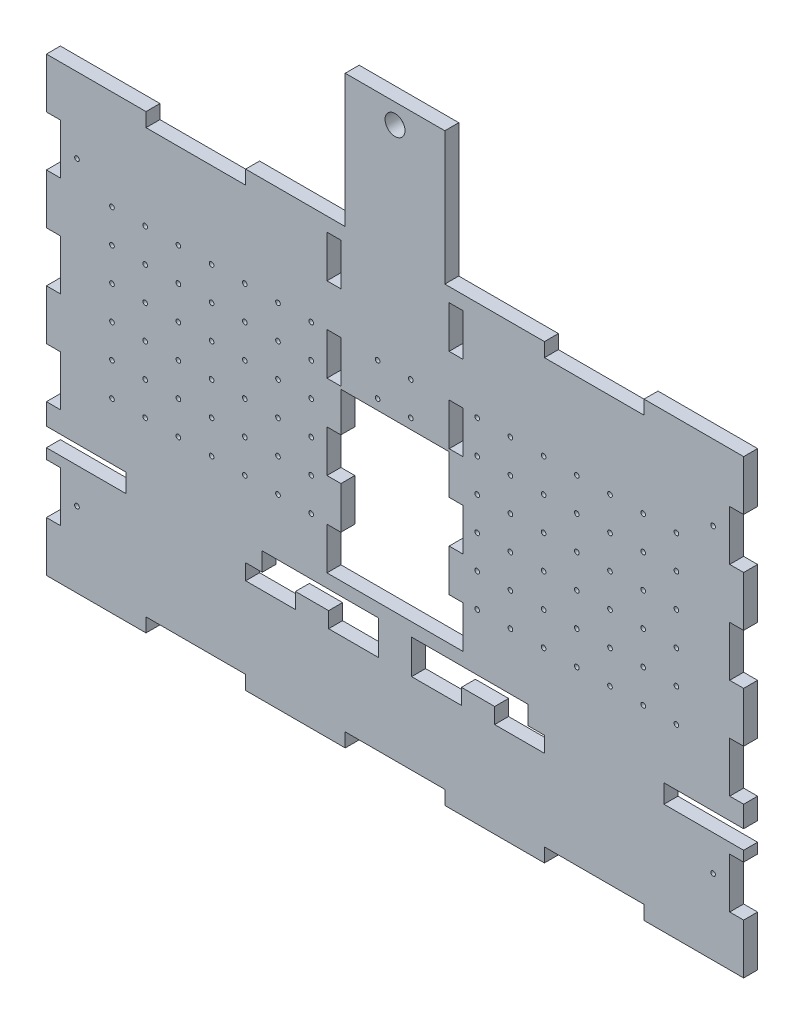
SolidWorks part; units mm, degrees
ref_plane "Front Plane" through (0, 0, 0) normal (0, 0, 1) x (1, 0, 0)
ref_plane "Top Plane" through (0, 0, 0) normal (0, 1, 0) x (1, 0, 0)
ref_plane "Right Plane" through (0, 0, 0) normal (1, 0, 0) x (0, 0, -1)
sketch "Sketch1" plane through (0, 0, 0) normal (0, 0, 1) x (1, 0, 0)
  line L1 (-127.8759, 88.4641) -> (138.8241, 88.4641)
  line L2 (-127.8759, 88.4641) -> (-127.8759, -84.2559)
  line L3 (-127.8759, -84.2559) -> (138.8241, -84.2559)
  line L4 (138.8241, 88.4641) -> (138.8241, -84.2559)
  dimension "D1" = 266.7
  dimension "D2" = 172.72
extrude "Boss-Extrude1" add sketch "Sketch1" along normal blind 5.334
sketch "Sketch2" plane through (0, 0, 5.334) normal (0, 0, 1) x (1, 0, 0)
  line L0 (-127.8759, -84.2559) -> (138.8241, -84.2559) construction
  line L1 (-89.7759, -84.2559) -> (-51.6759, -84.2559)
  line L2 (-89.7759, -84.2559) -> (-89.7759, -78.9219)
  line L3 (-89.7759, -78.9219) -> (-51.6759, -78.9219)
  line L4 (-51.6759, -84.2559) -> (-51.6759, -78.9219)
  line L5 (-89.7759, -78.9219) -> (-127.8759, -78.9219) construction
  line L6 (-13.5759, -84.2559) -> (24.5241, -84.2559)
  line L7 (-13.5759, -84.2559) -> (-13.5759, -78.9219)
  line L8 (-13.5759, -78.9219) -> (24.5241, -78.9219)
  line L9 (24.5241, -84.2559) -> (24.5241, -78.9219)
  line L10 (62.6241, -84.2559) -> (100.7241, -84.2559)
  line L11 (62.6241, -84.2559) -> (62.6241, -78.9219)
  line L12 (62.6241, -78.9219) -> (100.7241, -78.9219)
  line L13 (100.7241, -84.2559) -> (100.7241, -78.9219)
  line L14 (-127.8759, 88.4641) -> (-127.8759, -84.2559) construction
  line L15 (-51.6759, -78.9219) -> (-13.5759, -78.9219) construction
  line L16 (24.5241, -78.9219) -> (62.6241, -78.9219) construction
  line L17 (62.6241, -78.9219) -> (62.364, -79.7896) construction
  line L18 (100.7241, -78.9219) -> (138.8241, -78.9219) construction
  line L19 (138.8241, -84.2559) -> (138.8241, 88.4641) construction
  line L20 (-127.8759, 2.1041) -> (138.8241, 2.1041) construction
  line L21 (100.7241, 88.4641) -> (100.7241, 83.1301)
  line L22 (62.6241, 83.1301) -> (100.7241, 83.1301)
  line L23 (62.6241, 88.4641) -> (62.6241, 83.1301)
  line L24 (24.5241, 88.4641) -> (24.5241, 83.1301)
  line L25 (-13.5759, 83.1301) -> (24.5241, 83.1301)
  line L26 (-13.5759, 88.4641) -> (-13.5759, 83.1301)
  line L27 (-51.6759, 88.4641) -> (-51.6759, 83.1301)
  line L28 (-89.7759, 83.1301) -> (-51.6759, 83.1301)
  line L29 (-89.7759, 88.4641) -> (-89.7759, 83.1301)
  line L30 (62.6241, 88.4641) -> (100.7241, 88.4641)
  line L31 (-13.5759, 88.4641) -> (24.5241, 88.4641)
  line L32 (-89.7759, 88.4641) -> (-51.6759, 88.4641)
  dimension "D1" = 5.334
extrude "Cut-Extrude1" cut sketch "Sketch2" against normal through all
sketch "Sketch5" plane through (0, 0, 5.334) normal (0, 0, 1) x (1, 0, 0)
  line L0 (5.4741, 83.1301) -> (5.4741, -78.9219) construction
  line L1 (-13.5759, 83.1301) -> (24.5241, 83.1301) construction
  line L2 (24.5241, -78.9219) -> (-13.5759, -78.9219) construction
  line L3 (11.8241, -34.8224) -> (11.8241, -41.9344)
  line L4 (-45.3259, -34.8224) -> (-0.8759, -34.8224)
  line L5 (-45.3259, -34.8224) -> (-45.3259, -41.9344)
  line L6 (-45.3259, -41.9344) -> (-0.8759, -41.9344)
  line L7 (-0.8759, -34.8224) -> (-0.8759, -41.9344)
  line L8 (56.2741, -41.9344) -> (11.8241, -41.9344)
  line L9 (56.2741, -34.8224) -> (56.2741, -41.9344)
  line L10 (56.2741, -34.8224) -> (11.8241, -34.8224)
  line L11 (11.8241, -34.8224) -> (-0.8759, -34.8224) construction
  line L12 (-0.8759, -41.9344) -> (11.8241, -41.9344) construction
  line L13 (-141.8459, -34.8224) -> (-97.3959, -34.8224)
  line L14 (-141.8459, -34.8224) -> (-141.8459, -41.9344)
  line L15 (-141.8459, -41.9344) -> (-97.3959, -41.9344)
  line L16 (-97.3959, -34.8224) -> (-97.3959, -41.9344)
  line L18 (108.3441, -34.8224) -> (108.3441, -41.9344)
  line L19 (152.7941, -41.9344) -> (108.3441, -41.9344)
  line L20 (152.7941, -34.8224) -> (152.7941, -41.9344)
  line L21 (152.7941, -34.8224) -> (108.3441, -34.8224)
  dimension "D2" = 44.45
  dimension "D3" = 6.35
  dimension "D1" = 7.112
  dimension "D4" = 2
extrude "Cut-Extrude3" cut sketch "Sketch5" against normal through all
sketch "Sketch9" plane through (0, 0, 5.334) normal (0, 0, 1) x (1, 0, 0)
  line L0 (-127.8759, 88.4641) -> (-127.8759, -84.2559) construction
  line L1 (-127.8759, -65.0647) -> (-122.5419, -65.0647)
  line L2 (-127.8759, -65.0647) -> (-127.8759, -45.8736)
  line L3 (-127.8759, -45.8736) -> (-122.5419, -45.8736)
  line L4 (-122.5419, -65.0647) -> (-122.5419, -45.8736)
  line L5 (-122.5419, 69.273) -> (-122.5419, 88.4641) construction
  line L6 (-127.8759, -26.6825) -> (-122.5419, -26.6825)
  line L7 (-127.8759, -26.6825) -> (-127.8759, -7.4914)
  line L8 (-127.8759, -7.4914) -> (-122.5419, -7.4914)
  line L9 (-122.5419, -26.6825) -> (-122.5419, -7.4914)
  line L10 (-127.8759, 11.6997) -> (-122.5419, 11.6997)
  line L11 (-127.8759, 11.6997) -> (-127.8759, 30.8908)
  line L12 (-127.8759, 30.8908) -> (-122.5419, 30.8908)
  line L13 (-122.5419, 11.6997) -> (-122.5419, 30.8908)
  line L14 (-127.8759, 50.0819) -> (-122.5419, 50.0819)
  line L15 (-127.8759, 50.0819) -> (-127.8759, 69.273)
  line L16 (-127.8759, 69.273) -> (-122.5419, 69.273)
  line L17 (-122.5419, 50.0819) -> (-122.5419, 69.273)
  line L18 (-89.7759, 88.4641) -> (-127.8759, 88.4641) construction
  line L19 (-122.5419, 50.0819) -> (-122.5419, 30.8908) construction
  line L20 (-122.5419, 11.6997) -> (-122.5419, -7.4914) construction
  line L21 (-122.5419, -26.6825) -> (-122.5419, -45.8736) construction
  line L22 (-122.5419, -65.0647) -> (-122.5419, -84.2559) construction
  line L23 (-127.8759, -84.2559) -> (-89.7759, -84.2559) construction
  line L24 (5.4741, 83.1301) -> (5.4741, -78.9219) construction
  line L25 (-13.5759, 83.1301) -> (24.5241, 83.1301) construction
  line L26 (24.5241, -78.9219) -> (-13.5759, -78.9219) construction
  line L27 (133.4901, -65.0647) -> (133.4901, -84.2559) construction
  line L28 (133.4901, -26.6825) -> (133.4901, -45.8736) construction
  line L29 (133.4901, 11.6997) -> (133.4901, -7.4914) construction
  line L30 (133.4901, 50.0819) -> (133.4901, 30.8908) construction
  line L31 (133.4901, 69.273) -> (133.4901, 88.4641) construction
  line L32 (133.4901, 50.0819) -> (133.4901, 69.273)
  line L33 (138.8241, 69.273) -> (133.4901, 69.273)
  line L34 (138.8241, 50.0819) -> (138.8241, 69.273)
  line L35 (138.8241, 50.0819) -> (133.4901, 50.0819)
  line L36 (133.4901, 11.6997) -> (133.4901, 30.8908)
  line L37 (138.8241, 30.8908) -> (133.4901, 30.8908)
  line L38 (138.8241, 11.6997) -> (138.8241, 30.8908)
  line L39 (138.8241, 11.6997) -> (133.4901, 11.6997)
  line L40 (133.4901, -26.6825) -> (133.4901, -7.4914)
  line L41 (138.8241, -7.4914) -> (133.4901, -7.4914)
  line L42 (138.8241, -26.6825) -> (138.8241, -7.4914)
  line L43 (138.8241, -26.6825) -> (133.4901, -26.6825)
  line L44 (133.4901, -65.0647) -> (133.4901, -45.8736)
  line L45 (138.8241, -45.8736) -> (133.4901, -45.8736)
  line L46 (138.8241, -65.0647) -> (138.8241, -45.8736)
  line L47 (138.8241, -65.0647) -> (133.4901, -65.0647)
  dimension "D1" = 5.334
extrude "Cut-Extrude7" cut sketch "Sketch9" against normal through all
sketch "Sketch10" plane through (0, 88.4641, 0) normal (0, 1, 0) x (1, 0, 0)
  line L1 (24.5241, -5.334) -> (62.6241, -5.334)
  line L2 (24.5241, -5.334) -> (24.5241, 0)
  line L3 (24.5241, 0) -> (62.6241, 0)
  line L4 (62.6241, -5.334) -> (62.6241, 0)
extrude "Boss-Extrude2" add sketch "Sketch10" along normal blind 50.8
sketch "Sketch11" plane through (0, 0, 0) normal (0, 0, -1) x (-1, 0, 0)
  line L0 (-24.5241, 83.1301) -> (-24.5241, 139.2641) construction
  line L1 (-24.5241, 88.4641) -> (-31.1281, 88.4641)
  line L2 (-24.5241, 88.4641) -> (-24.5241, 129.1041)
  line L3 (-24.5241, 129.1041) -> (-31.1281, 129.1041)
  line L4 (-31.1281, 88.4641) -> (-31.1281, 129.1041)
  line L5 (13.5759, 88.4641) -> (51.6759, 88.4641) construction
  dimension "D1" = 6.604
  dimension "D2" = 40.64
  dimension "D3" = 0
extrude "Cut-Extrude8" cut sketch "Sketch11" against normal through all
sketch "Sketch12" plane through (0, 0, 5.334) normal (0, 0, 1) x (1, 0, 0)
  line L0 (62.6241, 139.2641) -> (62.6241, 83.1301) construction
  circle A0 centre (43.5741, 130.4765) radius 3.81
  dimension "D1" = 19.05
extrude "Cut-Extrude9" cut sketch "Sketch12" against normal through all
sketch "Sketch14" plane through (0, 0, 5.334) normal (0, 0, 1) x (1, 0, 0)
  line L0 (-89.7759, 88.4641) -> (-127.8759, 88.4641) construction
  circle A0 centre (-102.7976, 50.3641) radius 0.889
  circle A1 centre (-90.0976, 50.3641) radius 0.889
  circle A2 centre (-77.3976, 50.3641) radius 0.889
  circle A3 centre (-64.6976, 50.3641) radius 0.889
  circle A4 centre (-51.9976, 50.3641) radius 0.889
  circle A5 centre (-39.2976, 50.3641) radius 0.889
  circle A6 centre (-26.5976, 50.3641) radius 0.889
  circle A8 centre (-1.1976, 50.3641) radius 0.889
  circle A9 centre (11.5024, 50.3641) radius 0.889
  circle A11 centre (36.9024, 50.3641) radius 0.889
  circle A12 centre (49.6024, 50.3641) radius 0.889
  circle A13 centre (62.3024, 50.3641) radius 0.889
  circle A14 centre (75.0024, 50.3641) radius 0.889
  circle A15 centre (87.7024, 50.3641) radius 0.889
  circle A16 centre (100.4024, 50.3641) radius 0.889
  circle A17 centre (113.1024, 50.3641) radius 0.889
  circle A18 centre (-102.7976, 37.6641) radius 0.889
  circle A19 centre (-90.0976, 37.6641) radius 0.889
  circle A20 centre (-77.3976, 37.6641) radius 0.889
  circle A21 centre (-64.6976, 37.6641) radius 0.889
  circle A22 centre (-51.9976, 37.6641) radius 0.889
  circle A23 centre (-39.2976, 37.6641) radius 0.889
  circle A24 centre (-26.5976, 37.6641) radius 0.889
  circle A26 centre (-1.1976, 37.6641) radius 0.889
  circle A27 centre (11.5024, 37.6641) radius 0.889
  circle A29 centre (36.9024, 37.6641) radius 0.889
  circle A30 centre (49.6024, 37.6641) radius 0.889
  circle A31 centre (62.3024, 37.6641) radius 0.889
  circle A32 centre (75.0024, 37.6641) radius 0.889
  circle A33 centre (87.7024, 37.6641) radius 0.889
  circle A34 centre (100.4024, 37.6641) radius 0.889
  circle A35 centre (113.1024, 37.6641) radius 0.889
  circle A36 centre (-102.7976, 24.9641) radius 0.889
  circle A37 centre (-90.0976, 24.9641) radius 0.889
  circle A38 centre (-77.3976, 24.9641) radius 0.889
  circle A39 centre (-64.6976, 24.9641) radius 0.889
  circle A40 centre (-51.9976, 24.9641) radius 0.889
  circle A41 centre (-39.2976, 24.9641) radius 0.889
  circle A42 centre (-26.5976, 24.9641) radius 0.889
  circle A44 centre (-1.1976, 24.9641) radius 0.889
  circle A45 centre (11.5024, 24.9641) radius 0.889
  circle A47 centre (36.9024, 24.9641) radius 0.889
  circle A48 centre (49.6024, 24.9641) radius 0.889
  circle A49 centre (62.3024, 24.9641) radius 0.889
  circle A50 centre (75.0024, 24.9641) radius 0.889
  circle A51 centre (87.7024, 24.9641) radius 0.889
  circle A52 centre (100.4024, 24.9641) radius 0.889
  circle A53 centre (113.1024, 24.9641) radius 0.889
  circle A54 centre (-102.7976, 12.2641) radius 0.889
  circle A55 centre (-90.0976, 12.2641) radius 0.889
  circle A56 centre (-77.3976, 12.2641) radius 0.889
  circle A57 centre (-64.6976, 12.2641) radius 0.889
  circle A58 centre (-51.9976, 12.2641) radius 0.889
  circle A59 centre (-39.2976, 12.2641) radius 0.889
  circle A60 centre (-26.5976, 12.2641) radius 0.889
  circle A65 centre (36.9024, 12.2641) radius 0.889
  circle A66 centre (49.6024, 12.2641) radius 0.889
  circle A67 centre (62.3024, 12.2641) radius 0.889
  circle A68 centre (75.0024, 12.2641) radius 0.889
  circle A69 centre (87.7024, 12.2641) radius 0.889
  circle A70 centre (100.4024, 12.2641) radius 0.889
  circle A71 centre (113.1024, 12.2641) radius 0.889
  circle A72 centre (-102.7976, -0.4359) radius 0.889
  circle A73 centre (-90.0976, -0.4359) radius 0.889
  circle A74 centre (-77.3976, -0.4359) radius 0.889
  circle A75 centre (-64.6976, -0.4359) radius 0.889
  circle A76 centre (-51.9976, -0.4359) radius 0.889
  circle A77 centre (-39.2976, -0.4359) radius 0.889
  circle A78 centre (-26.5976, -0.4359) radius 0.889
  circle A79 centre (-13.8976, -0.4359) radius 0.889
  circle A80 centre (-1.1976, -0.4359) radius 0.889
  circle A81 centre (11.5024, -0.4359) radius 0.889
  circle A82 centre (24.2024, -0.4359) radius 0.889
  circle A83 centre (36.9024, -0.4359) radius 0.889
  circle A84 centre (49.6024, -0.4359) radius 0.889
  circle A85 centre (62.3024, -0.4359) radius 0.889
  circle A86 centre (75.0024, -0.4359) radius 0.889
  circle A87 centre (87.7024, -0.4359) radius 0.889
  circle A88 centre (100.4024, -0.4359) radius 0.889
  circle A89 centre (113.1024, -0.4359) radius 0.889
  circle A90 centre (-102.7976, -13.1359) radius 0.889
  circle A91 centre (-90.0976, -13.1359) radius 0.889
  circle A92 centre (-77.3976, -13.1359) radius 0.889
  circle A93 centre (-64.6976, -13.1359) radius 0.889
  circle A94 centre (-51.9976, -13.1359) radius 0.889
  circle A95 centre (-39.2976, -13.1359) radius 0.889
  circle A96 centre (-26.5976, -13.1359) radius 0.889
  circle A97 centre (-13.8976, -13.1359) radius 0.889
  circle A98 centre (-1.1976, -13.1359) radius 0.889
  circle A99 centre (11.5024, -13.1359) radius 0.889
  circle A100 centre (24.2024, -13.1359) radius 0.889
  circle A101 centre (36.9024, -13.1359) radius 0.889
  circle A102 centre (49.6024, -13.1359) radius 0.889
  circle A103 centre (62.3024, -13.1359) radius 0.889
  circle A104 centre (75.0024, -13.1359) radius 0.889
  circle A105 centre (87.7024, -13.1359) radius 0.889
  circle A106 centre (100.4024, -13.1359) radius 0.889
  circle A107 centre (113.1024, -13.1359) radius 0.889
  circle A108 centre (-1.1976, 12.2641) radius 0.889 [skipped]
  circle A110 centre (11.5024, 12.2641) radius 0.889 [skipped]
  circle A116 centre (24.2024, 50.3641) radius 0.889 [skipped]
  circle A117 centre (-13.8976, 50.3641) radius 0.889 [skipped]
  dimension "D1" = 18
  dimension "D2" = 38.1
  dimension "D4" = 1.778
  dimension "D3" = 6
extrude "Cut-Extrude11" cut sketch "Sketch14" against normal through all
sketch "Sketch15" plane through (0, 0, 5.334) normal (0, 0, 1) x (1, 0, 0)
  line L1 (31.1281, 129.1041) -> (24.5241, 129.1041)
  line L2 (31.1281, 129.1041) -> (31.1281, 139.2641)
  line L3 (31.1281, 139.2641) -> (24.5241, 139.2641)
  line L4 (24.5241, 129.1041) -> (24.5241, 139.2641)
extrude "Cut-Extrude12" cut sketch "Sketch15" against normal through all
sketch "Sketch16" plane through (0, 0, 5.334) normal (0, 0, 1) x (1, 0, 0)
  line L0 (5.4741, 83.1301) -> (5.4741, -78.9219) construction
  line L1 (-15.2269, 33.7576) -> (26.1751, 33.7576)
  line L2 (-15.2269, 33.7576) -> (-15.2269, -29.7424)
  line L3 (-15.2269, -29.7424) -> (26.1751, -29.7424)
  line L4 (26.1751, 33.7576) -> (26.1751, -29.7424)
  line L5 (-13.5759, 83.1301) -> (24.5241, 83.1301) construction
  line L6 (24.5241, -78.9219) -> (-13.5759, -78.9219) construction
  line L8 (-0.8759, -34.8224) -> (-45.3259, -34.8224) construction
  dimension "D1" = 63.5
  dimension "D2" = 41.402
  dimension "D3" = 20.701
  dimension "D4" = 5.08
extrude "Cut-Extrude13" cut sketch "Sketch16" against normal through all
sketch "Sketch17" plane through (0, 0, 5.334) normal (0, 0, 1) x (1, 0, 0)
  line L0 (-15.2269, 33.7576) -> (-15.2269, -29.7424) construction
  line L1 (-15.2269, -29.7424) -> (-20.5609, -29.7424)
  line L2 (-15.2269, -29.7424) -> (-15.2269, -13.6178)
  line L3 (-15.2269, -13.6178) -> (-20.5609, -13.6178)
  line L4 (-20.5609, -29.7424) -> (-20.5609, -13.6178)
  line L5 (-15.2269, 2.5069) -> (-20.5609, 2.5069)
  line L6 (-15.2269, 2.5069) -> (-15.2269, 18.6315)
  line L7 (-15.2269, 18.6315) -> (-20.5609, 18.6315)
  line L8 (-20.5609, 2.5069) -> (-20.5609, 18.6315)
  line L9 (-20.5609, -13.6178) -> (-20.5609, 2.5069) construction
  line L10 (-20.5609, 50.8808) -> (-15.2269, 50.8808)
  line L11 (-20.5609, 50.8808) -> (-20.5609, 34.7562)
  line L12 (-20.5609, 34.7562) -> (-15.2269, 34.7562)
  line L13 (-15.2269, 50.8808) -> (-15.2269, 34.7562)
  line L14 (-20.5609, 67.0055) -> (-15.2269, 67.0055)
  line L15 (-20.5609, 67.0055) -> (-20.5609, 83.1301)
  line L16 (-20.5609, 83.1301) -> (-15.2269, 83.1301)
  line L17 (-15.2269, 67.0055) -> (-15.2269, 83.1301)
  line L18 (-20.5609, 18.6315) -> (-20.5609, 34.7562) construction
  line L19 (-20.5609, 67.0055) -> (-20.5609, 50.8808) construction
  line L20 (5.4741, 83.1301) -> (5.4741, -78.9219) construction
  line L21 (-13.5759, 83.1301) -> (24.5241, 83.1301) construction
  line L22 (24.5241, -78.9219) -> (-13.5759, -78.9219) construction
  line L23 (31.5091, 67.0055) -> (31.5091, 50.8808) construction
  line L24 (31.5091, 18.6315) -> (31.5091, 34.7562) construction
  line L25 (31.5091, -13.6178) -> (31.5091, 2.5069) construction
  line L26 (26.1751, 67.0055) -> (26.1751, 83.1301)
  line L27 (31.5091, 83.1301) -> (26.1751, 83.1301)
  line L28 (31.5091, 67.0055) -> (31.5091, 83.1301)
  line L29 (31.5091, 67.0055) -> (26.1751, 67.0055)
  line L30 (26.1751, 50.8808) -> (26.1751, 34.7562)
  line L31 (31.5091, 34.7562) -> (26.1751, 34.7562)
  line L32 (31.5091, 50.8808) -> (31.5091, 34.7562)
  line L33 (31.5091, 50.8808) -> (26.1751, 50.8808)
  line L34 (31.5091, 2.5069) -> (31.5091, 18.6315)
  line L35 (26.1751, 18.6315) -> (31.5091, 18.6315)
  line L36 (26.1751, 2.5069) -> (26.1751, 18.6315)
  line L37 (26.1751, 2.5069) -> (31.5091, 2.5069)
  line L38 (31.5091, -29.7424) -> (31.5091, -13.6178)
  line L39 (26.1751, -13.6178) -> (31.5091, -13.6178)
  line L40 (26.1751, -29.7424) -> (26.1751, -13.6178)
  line L41 (26.1751, -29.7424) -> (31.5091, -29.7424)
  dimension "D1" = 0
  dimension "D2" = 5.334
  dimension "D3" = 5.334
  dimension "D4" = 5.334
extrude "Cut-Extrude14" cut sketch "Sketch17" against normal through all
sketch "Sketch18" plane through (0, 0, 5.334) normal (0, 0, 1) x (1, 0, 0)
  line L0 (24.5241, 83.1301) -> (24.5241, 148.9274) construction
  line L1 (31.1281, 139.2641) -> (62.6241, 139.2641) construction
  line L2 (-13.5759, 83.1301) -> (24.5241, 83.1301)
  line L3 (-13.5759, 83.1301) -> (-13.5759, 139.2641)
  line L4 (-13.5759, 139.2641) -> (24.5241, 139.2641)
  line L5 (24.5241, 83.1301) -> (24.5241, 139.2641)
  dimension "D1" = 0
extrude "Boss-Extrude3" add sketch "Sketch18" against normal blind 5.334
sketch "Sketch19" plane through (0, 0, 5.334) normal (0, 0, 1) x (1, 0, 0)
  line L1 (31.1281, 88.4641) -> (65.8849, 88.4641)
  line L2 (31.1281, 88.4641) -> (31.1281, 143.4078)
  line L3 (31.1281, 143.4078) -> (65.8849, 143.4078)
  line L4 (65.8849, 88.4641) -> (65.8849, 143.4078)
extrude "Cut-Extrude15" cut sketch "Sketch19" against normal through all
sketch "Sketch20" plane through (0, 0, 5.334) normal (0, 0, 1) x (1, 0, 0)
  line L0 (5.4741, 139.2641) -> (5.4741, 29.9476) construction
  line L1 (24.5241, 139.2641) -> (-13.5759, 139.2641) construction
  circle A0 centre (5.4741, 131.6441) radius 3.81
  dimension "D1" = 7.62
  dimension "D3" = 7.62
  dimension "D2" = 0
extrude "Cut-Extrude16" cut sketch "Sketch20" against normal through all contours A0
sketch "Sketch21" plane through (0, 0, 5.334) normal (0, 0, 1) x (1, 0, 0)
  line L0 (133.4901, 59.6775) -> (-122.5419, 59.6775) construction
  line L1 (133.4901, 69.273) -> (133.4901, 50.0819) construction
  line L2 (-122.5419, 50.0819) -> (-122.5419, 69.273) construction
  line L3 (-122.5419, -55.4692) -> (133.4901, -55.4692) construction
  line L4 (-122.5419, -65.0647) -> (-122.5419, -45.8736) construction
  line L5 (133.4901, -45.8736) -> (133.4901, -65.0647) construction
  line L6 (138.8241, 2.1041) -> (-127.8759, 2.1041) construction
  line L7 (138.8241, -7.4914) -> (138.8241, 11.6997) construction
  line L8 (-127.8759, 11.6997) -> (-127.8759, -7.4914) construction
  line L9 (5.4741, 139.2641) -> (5.4741, -78.9219) construction
  line L10 (24.5241, 139.2641) -> (-13.5759, 139.2641) construction
  line L11 (24.5241, -78.9219) -> (-13.5759, -78.9219) construction
  circle A0 centre (127.1401, 59.6775) radius 0.889
  circle A1 centre (-116.1919, 59.6775) radius 0.889
  circle A2 centre (-116.1919, -55.4692) radius 0.889
  circle A3 centre (127.1401, -55.4692) radius 0.889
  dimension "D1" = 1.778
  dimension "D2" = 0
  dimension "D3" = 6.35
extrude "Cut-Extrude17" cut sketch "Sketch21" against normal through all
sketch "Sketch22" plane through (0, 0, 0) normal (0, 0, -1) x (-1, 0, 0)
  line L0 (-11.8241, -41.9344) -> (-56.2741, -41.9344) construction
  line L1 (-30.8741, -41.9344) -> (-11.8241, -41.9344)
  line L2 (-30.8741, -41.9344) -> (-30.8741, -47.9281)
  line L3 (-30.8741, -47.9281) -> (-11.8241, -47.9281)
  line L4 (-11.8241, -41.9344) -> (-11.8241, -47.9281)
  line L5 (-11.8241, -34.8224) -> (-11.8241, -41.9344) construction
  line L6 (-62.6241, -47.9281) -> (-43.5741, -47.9281)
  line L7 (-43.5741, -41.9344) -> (-43.5741, -47.9281)
  line L8 (-62.6241, -41.9344) -> (-43.5741, -41.9344)
  line L9 (-62.6241, -41.9344) -> (-62.6241, -47.9281)
  line L10 (-5.4741, -78.9219) -> (-5.4741, 95.0308) construction
  line L11 (-24.5241, -78.9219) -> (13.5759, -78.9219) construction
  line L12 (51.6759, -41.9344) -> (51.6759, -47.9281)
  line L13 (51.6759, -41.9344) -> (32.6259, -41.9344)
  line L14 (32.6259, -41.9344) -> (32.6259, -47.9281)
  line L15 (51.6759, -47.9281) -> (32.6259, -47.9281)
  line L16 (0.8759, -41.9344) -> (0.8759, -47.9281)
  line L17 (19.9259, -47.9281) -> (0.8759, -47.9281)
  line L18 (19.9259, -41.9344) -> (19.9259, -47.9281)
  line L19 (19.9259, -41.9344) -> (0.8759, -41.9344)
  dimension "D1" = 19.05
  dimension "D2" = 0
  dimension "D3" = 2
extrude "Cut-Extrude18" cut sketch "Sketch22" against normal through all
equation "\"MDF\"= .21in"
equation "\"Foamcore\"= .13in"
equation "\"Gmaterial\"= \"MDF\""
equation "\"D1@Boss-Extrude1\"=\"MDF\""
equation "\"D1@Sketch2\"=\"MDF\""
equation "\"D1@Sketch5\"=\"MDF\"+0.07"
equation "\"D1@Sketch9\"=\"MDF\""
equation "\"D1@Sketch11\"=\"MDF\"+.05"
equation "\"D2@Sketch17\"=\"MDF\""
equation "\"D3@Sketch17\"=\"MDF\""
equation "\"D4@Sketch17\"=\"MDF\""
equation "\"D1@Boss-Extrude3\"=\"MDF\""
